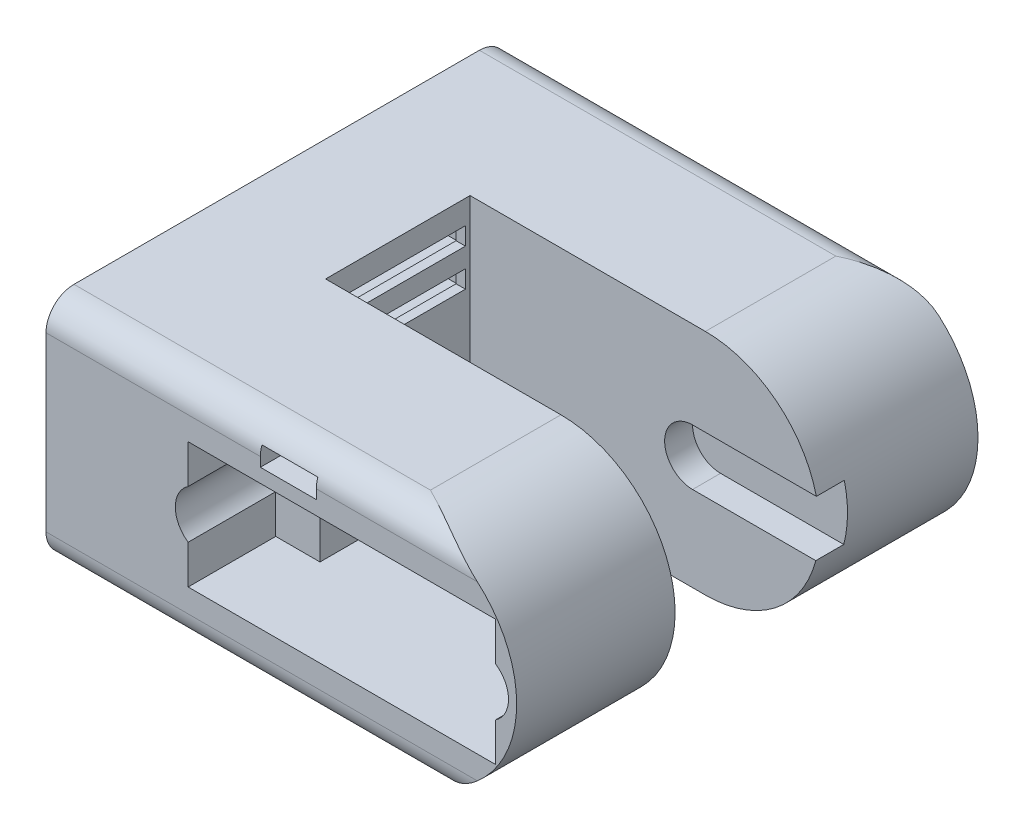
SolidWorks part; units mm, degrees
ref_plane "Спереди" through (0, 0, 0) normal (0, 0, 1) x (1, 0, 0)
ref_plane "Сверху" through (0, 0, 0) normal (0, 1, 0) x (1, 0, 0)
ref_plane "Справа" through (0, 0, 0) normal (1, 0, 0) x (0, 0, -1)
sketch "Эскиз1" plane through (0, 0, 0) normal (1, 0, 0) x (0, 0, -1)
  line L0 (-1050, 0) -> (48950, 0) construction
  line L1 (0, -1021.7777) -> (0, 48978.2223) construction
  line L2 (-24.75, -12.25) -> (24.75, -12.25)
  line L3 (-24.75, -12.25) -> (-24.75, 12.25)
  line L4 (-24.75, 12.25) -> (24.75, 12.25)
  line L5 (24.75, -12.25) -> (24.75, 12.25)
  line L6 (-24.75, -12.25) -> (24.75, 12.25) construction
  line L7 (-24.75, 12.25) -> (24.75, -12.25) construction
  point P3 (0, 0)
  dimension "D1" = 24.5
  dimension "D2" = 49.5
extrude "Бобышка-Вытянуть1" add sketch "Эскиз1" along normal blind 36
sketch "Эскиз2" plane through (0, 0, 0) normal (-1, 0, 0) x (0, 0, 1)
  line L1 (-24.75, -12.25) -> (-24.75, 12.25) construction
  line L2 (24.75, 12.25) -> (24.75, -12.25) construction
  line L3 (24.75, -12.25) -> (-24.75, -12.25) construction
  circle A0 centre (-20, -7.25) radius 2.5
  circle A1 centre (20, -7.25) radius 2.5
  dimension "D3" = 5
  dimension "D1" = 5
  dimension "D2" = 4.75
  dimension "D4" = 4.75
  dimension "D5" = 5
extrude "Вырез-Вытянуть1" cut sketch "Эскиз2" against normal blind 3
sketch "Эскиз3" plane through (0, 0, 0) normal (-1, 0, 0) x (0, 0, 1)
  line L0 (0, -1000) -> (0, 49000) construction
  line L1 (-7.7, 3.4) -> (7.7, 3.4)
  line L2 (-7.7, 7.4) -> (7.7, 7.4)
  line L3 (-7.7, 7.4) -> (-7.7, 10.1)
  line L4 (-7.7, 10.1) -> (7.7, 10.1)
  line L5 (7.7, 7.4) -> (7.7, 10.1)
  line L6 (-7.7, 7.4) -> (7.7, 10.1) construction
  line L7 (-7.7, 10.1) -> (7.7, 7.4) construction
  line L8 (-24.75, 12.25) -> (24.75, 12.25) construction
  line L9 (-7.7, 3.4) -> (-7.7, 6.1)
  line L10 (-7.7, 6.1) -> (7.7, 6.1)
  line L11 (7.7, 3.4) -> (7.7, 6.1)
  line L12 (-7.7, 3.4) -> (7.7, 6.1) construction
  line L13 (-7.7, 6.1) -> (7.7, 3.4) construction
  point P1 (0, 8.75)
  point P11 (0, 4.75)
  dimension "D1" = 15.4
  dimension "D2" = 2.7
  dimension "D3" = 2.15
  dimension "D4" = 2.7
  dimension "D5" = 4
extrude "Вырез-Вытянуть2" cut sketch "Эскиз3" against normal blind 12
sketch "Эскиз9" plane through (0, 12.25, 0) normal (0, -1, 0) x (1, 0, 0)
  line L0 (-1000, 0) -> (49000, 0) construction
  line L6 (36, 24.75) -> (13, 24.75)
  line L7 (36, 24.75) -> (36, -24.75)
  line L8 (36, -24.75) -> (13, -24.75)
  line L10 (13, 24.75) -> (13, -24.75)
  line L11 (0, 24.75) -> (0, -24.75) construction
  dimension "D1" = 13
  dimension "D2" = 24.75
  dimension "D3" = 49.5
extrude "Вырез-Вытянуть9" cut sketch "Эскиз9" along normal blind 24.5
sketch "Эскиз11" plane through (12, 0, 0) normal (-1, 0, 0) x (0, 0, 1)
  line L0 (-1007.6, 8.75) -> (48992.4, 8.75) construction
  line L1 (-7.25, 9.7) -> (7.25, 9.7)
  line L2 (-7.25, 9.7) -> (-7.25, 7.8)
  line L3 (-7.25, 7.8) -> (7.25, 7.8)
  line L4 (7.25, 9.7) -> (7.25, 7.8)
  line L5 (-7.25, 9.7) -> (7.25, 7.8) construction
  line L6 (-7.25, 7.8) -> (7.25, 9.7) construction
  line L7 (-7.7, 10.1) -> (-7.7, 7.4) construction
  line L8 (-1007.6, 4.75) -> (48992.4, 4.75) construction
  line L9 (-7.7, 6.1) -> (-7.7, 3.4) construction
  line L10 (0, -990) -> (0, 49010) construction
  line L11 (7.7, 10.1) -> (-7.7, 10.1) construction
  line L13 (-7.25, 5.7) -> (7.25, 5.7)
  line L14 (-7.25, 5.7) -> (-7.25, 3.8)
  line L15 (-7.25, 3.8) -> (7.25, 3.8)
  line L16 (7.25, 5.7) -> (7.25, 3.8)
  line L17 (-7.25, 5.7) -> (7.25, 3.8) construction
  line L18 (-7.25, 3.8) -> (7.25, 5.7) construction
  point P0 (0, 8.75)
  point P10 (-7.7, 8.75)
  point P15 (-7.7, 4.75)
  point P16 (0, 4.75)
  point P20 (0, 10.1)
  dimension "D1" = 1.9
  dimension "D2" = 14.5
  dimension "D3" = 1.9
extrude "Вырез-Вытянуть8" cut sketch "Эскиз11" against normal blind 2
fillet "Скругление1" radius 3 4 edges at (6.5, 12.25, -24.75) (6.5, -12.25, -24.75) (6.5, 12.25, 24.75) (6.5, -12.25, 24.75)
sketch "Эскиз12" plane through (13, 0, 0) normal (1, 0, 0) x (0, 0, -1)
  line L0 (-7.75, 12.25) -> (-7.75, -12.25)
  line L1 (-21.75, 12.25) -> (21.75, 12.25) construction
  line L2 (-21.75, -12.25) -> (21.75, -12.25) construction
  line L3 (-7.75, -12.25) -> (-21.75, -12.25)
  line L5 (-21.75, 12.25) -> (-7.75, 12.25)
  line L6 (-24.75, -9.25) -> (-24.75, 9.25) construction
  line L7 (-24.75, -9.25) -> (-24.75, 9.25)
  line L8 (21.75, 12.25) -> (7.75, 12.25)
  line L9 (7.75, 12.25) -> (7.75, -12.25)
  line L10 (7.75, -12.25) -> (21.75, -12.25)
  line L11 (24.75, -9.25) -> (24.75, 9.25) construction
  line L12 (24.75, -9.25) -> (24.75, 9.25)
  arc A0 (-24.75, -9.25) -> (-21.75, -12.25) centre (-21.75, -9.25) ccw construction
  arc A1 (-21.75, 12.25) -> (-24.75, 9.25) centre (-21.75, 9.25) ccw construction
  arc A2 (-24.75, -9.25) -> (-21.75, -12.25) centre (-21.75, -9.25) ccw
  arc A3 (-21.75, 12.25) -> (-24.75, 9.25) centre (-21.75, 9.25) ccw
  arc A4 (24.75, 9.25) -> (21.75, 12.25) centre (21.75, 9.25) ccw construction
  arc A5 (21.75, -12.25) -> (24.75, -9.25) centre (21.75, -9.25) ccw construction
  arc A6 (24.75, 9.25) -> (21.75, 12.25) centre (21.75, 9.25) ccw
  arc A7 (21.75, -12.25) -> (24.75, -9.25) centre (21.75, -9.25) ccw
  dimension "D1" = 17
extrude "Бобышка-Вытянуть2" add sketch "Эскиз12" along normal blind 37.5
sketch "Эскиз13" plane through (0, 0, 7.75) normal (0, 0, -1) x (-1, 0, 0)
  line L0 (-1048, 0) -> (48952, 0) construction
  line L1 (-50.5, -12.25) -> (-50.5, 12.25) construction
  line L2 (-31.75, -987.75) -> (-31.75, 49012.25) construction
  line L3 (-50.5, 12.25) -> (-13, 12.25) construction
  line L5 (-43.5, -6.75) -> (-20, -6.75)
  line L6 (-43.5, -6.75) -> (-43.5, 6.75)
  line L7 (-43.5, 6.75) -> (-20, 6.75)
  line L8 (-20, -6.75) -> (-20, 6.75)
  line L9 (-43.5, -6.75) -> (-20, 6.75) construction
  line L10 (-43.5, 6.75) -> (-20, -6.75) construction
  point P5 (-50.5, 0)
  point P6 (-31.75, 0)
  point P10 (-31.75, 12.25)
  dimension "D1" = 23.5
  dimension "D2" = 13.5
extrude "Вырез-Вытянуть10" cut sketch "Эскиз13" against normal blind 7.6
sketch "Эскиз14" plane through (0, 0, 15.35) normal (0, 0, -1) x (-1, 0, 0)
  line L0 (-1042.25, 0) -> (48957.75, 0) construction
  line L1 (-43.5, 6.75) -> (-43.5, -6.75) construction
  line L2 (-31.75, -993.25) -> (-31.75, 49006.75) construction
  line L3 (-20, 6.75) -> (-43.5, 6.75) construction
  line L5 (-48.25, -6.75) -> (-15.25, -6.75)
  line L6 (-48.25, -6.75) -> (-48.25, 6.75)
  line L7 (-48.25, 6.75) -> (-15.25, 6.75)
  line L8 (-15.25, -6.75) -> (-15.25, 6.75)
  line L9 (-48.25, -6.75) -> (-15.25, 6.75) construction
  line L10 (-48.25, 6.75) -> (-15.25, -6.75) construction
  point P5 (-43.5, 0)
  point P6 (-31.75, 0)
  point P10 (-31.75, 6.75)
  dimension "D1" = 33
extrude "Вырез-Вытянуть11" cut sketch "Эскиз14" against normal up to surface (9.4 mm away) up to face at (25.25, 0, 24.75)
sketch "Эскиз16" plane through (0, 0, 24.75) normal (0, 0, 1) x (1, 0, 0)
  line L0 (17, -1000.4904) -> (17, 48999.5096) construction
  line L1 (46.5, -999.8452) -> (46.5, 49000.1548) construction
  line L2 (20, -6.75) -> (20, 6.75) construction
  line L3 (43.5, 6.75) -> (43.5, -6.75) construction
  line L4 (-981.25, 0) -> (49018.75, 0) construction
  circle A0 centre (17, 0) radius 1.45
  circle A1 centre (46.5, 0) radius 1.45
  point P11 (20, 0)
  dimension "D3" = 2.9
  dimension "D1" = 3
  dimension "D2" = 3
extrude "Вырез-Вытянуть12" cut sketch "Эскиз16" against normal up to surface (17 mm away) up to face at (31.75, 0, 7.75)
sketch "Эскиз17" plane through (0, 0, 24.75) normal (0, 0, 1) x (1, 0, 0)
  circle A0 centre (17, 0) radius 3.125
  circle A1 centre (46.5, 0) radius 3.125
  dimension "D1" = 6.25
extrude "Вырез-Вытянуть13" cut sketch "Эскиз17" against normal up to surface (9.4 mm away) up to face at (18.45, 0, 15.35)
sketch "Эскиз18" plane through (0, 0, -7.75) normal (0, 0, 1) x (1, 0, 0)
  line L1 (50.5, 9.25) -> (50.5, -9.25) construction
  line L3 (50.5, -12.25) -> (0, -12.25) construction
  line L5 (36.875, 2.875) -> (50.5, 2.875)
  line L7 (36.875, -3.125) -> (50.5, -3.125)
  line L8 (50.5, 2.875) -> (50.5, -3.125)
  arc A0 (36.875, 2.875) -> (36.875, -3.125) centre (36.875, -0.125) ccw
  point P7 (36.875, -3.125)
  dimension "D3" = 6
  dimension "D1" = 13.625
  dimension "D2" = 12.125
extrude "Вырез-Вытянуть14" cut sketch "Эскиз18" against normal blind 3
sketch "Эскиз19" plane through (0, 0, -24.75) normal (0, 0, -1) x (-1, 0, 0)
  line L0 (0, 12.25) -> (-50.5, 12.25) construction
  line L1 (-50.5, -12.25) -> (0, -12.25) construction
  line L2 (-38.25, 12.25) -> (-51.5, 12.25)
  line L3 (-51.5, 12.25) -> (-51.5, -12.25)
  line L4 (-51.5, -12.25) -> (-38.25, -12.25)
  line L5 (-50.5, 9.25) -> (-50.5, -9.25) construction
  arc A0 (-38.25, 12.25) -> (-38.25, -12.25) centre (-38.25, 0) ccw
  point P11 (-39.462, 12.25)
  dimension "D1" = 1
extrude "Вырез-Вытянуть15" cut sketch "Эскиз19" against normal up to surface (49.5 mm away) up to face at (31.75, 0, 24.75)
sketch "Эскиз20" plane through (0, 0, 24.75) normal (0, 0, 1) x (1, 0, 0)
  line L0 (20, -6.75) -> (20, 6.75) construction
  line L1 (23, 8.25) -> (29, 8.25)
  line L2 (23, 8.25) -> (23, 10.25)
  line L3 (23, 10.25) -> (29, 10.25)
  line L4 (29, 8.25) -> (29, 10.25)
  line L5 (48.25, 6.75) -> (15.25, 6.75) construction
  dimension "D1" = 3
  dimension "D2" = 6
  dimension "D3" = 2
  dimension "D4" = 1.5
extrude "Вырез-Вытянуть16" cut sketch "Эскиз20" against normal blind 19
